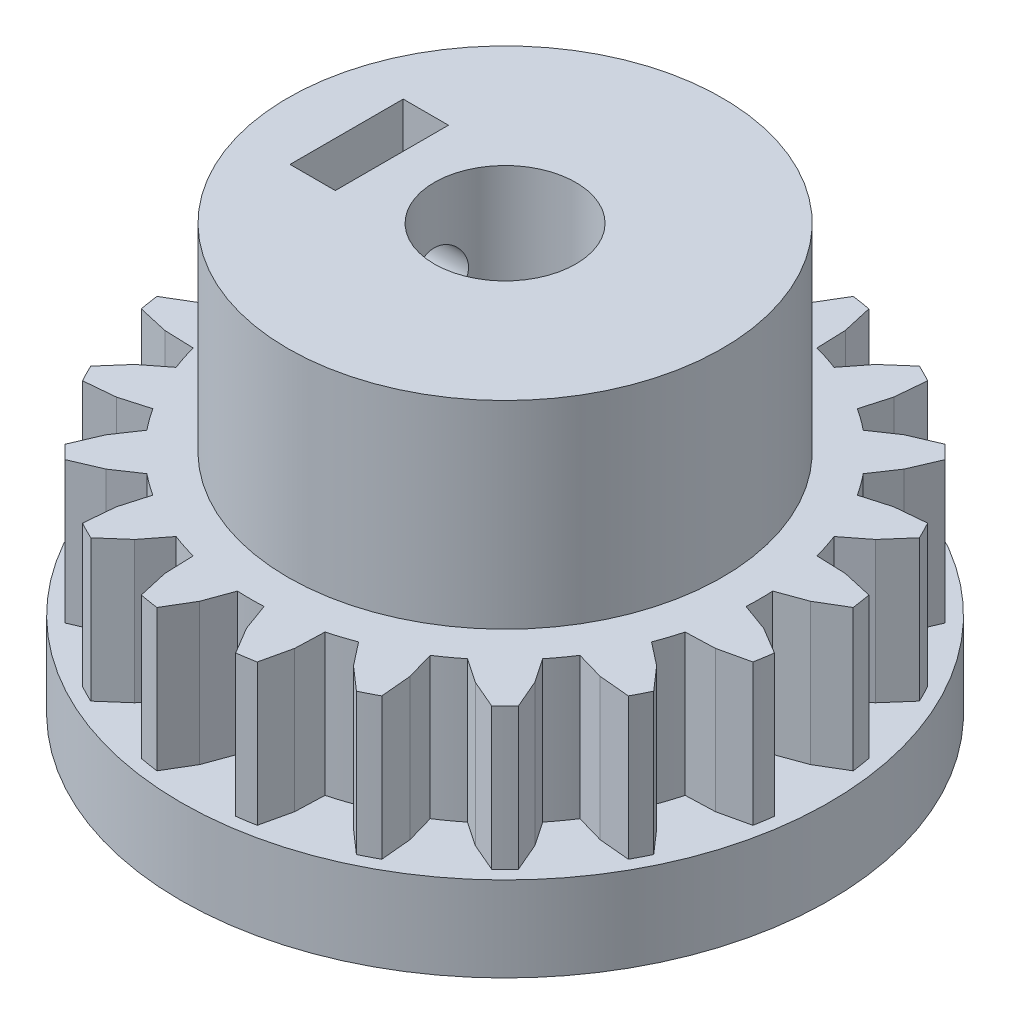
SolidWorks part; units mm, degrees
ref_plane "Ön Düzlem" through (0, 0, 0) normal (0, 0, 1) x (1, 0, 0)
ref_plane "Üst Düzlem" through (0, 0, 0) normal (0, 1, 0) x (1, 0, 0)
ref_plane "Sağ Düzlem" through (0, 0, 0) normal (1, 0, 0) x (0, 0, -1)
sketch "Çizim1" plane through (0, 0, 0) normal (0, 1, 0) x (1, 0, 0)
  line L0 (10.9117, -1.3908) -> (9.9657, -0.827)
  line L1 (9.9657, -0.827) -> (8.9877, -0.471)
  line L2 (8.9877, 0.471) -> (9.9657, 0.827)
  line L3 (9.9657, 0.827) -> (10.9117, 1.3908)
  line L4 (10.8074, 2.0492) -> (9.7335, 2.293)
  line L5 (9.7335, 2.293) -> (8.6933, 2.3294)
  line L6 (8.4022, 3.2253) -> (9.2224, 3.8661)
  line L7 (9.2224, 3.8661) -> (9.9479, 4.6946)
  line L8 (9.6452, 5.2886) -> (8.5486, 5.1886)
  line L9 (8.5486, 5.1886) -> (7.548, 4.9018)
  line L10 (6.9943, 5.6639) -> (7.5763, 6.5268)
  line L11 (7.5763, 6.5268) -> (8.0103, 7.5389)
  line L12 (7.5389, 8.0103) -> (6.5268, 7.5763)
  line L13 (6.5268, 7.5763) -> (5.6639, 6.9943)
  line L14 (4.9018, 7.548) -> (5.1886, 8.5486)
  line L15 (5.1886, 8.5486) -> (5.2886, 9.6452)
  line L16 (4.6946, 9.9479) -> (3.8661, 9.2224)
  line L17 (3.8661, 9.2224) -> (3.2253, 8.4022)
  line L18 (2.3294, 8.6933) -> (2.293, 9.7335)
  line L19 (2.293, 9.7335) -> (2.0492, 10.8074)
  line L20 (1.3908, 10.9117) -> (0.827, 9.9657)
  line L21 (0.827, 9.9657) -> (0.471, 8.9877)
  line L22 (-0.471, 8.9877) -> (-0.827, 9.9657)
  line L23 (-0.827, 9.9657) -> (-1.3908, 10.9117)
  line L24 (-2.0492, 10.8074) -> (-2.293, 9.7335)
  line L25 (-2.293, 9.7335) -> (-2.3294, 8.6933)
  line L26 (-3.2253, 8.4022) -> (-3.8661, 9.2224)
  line L27 (-3.8661, 9.2224) -> (-4.6946, 9.9479)
  line L28 (-5.2886, 9.6452) -> (-5.1886, 8.5486)
  line L29 (-5.1886, 8.5486) -> (-4.9018, 7.548)
  line L30 (-5.6639, 6.9943) -> (-6.5268, 7.5763)
  line L31 (-6.5268, 7.5763) -> (-7.5389, 8.0103)
  line L32 (-8.0103, 7.5389) -> (-7.5763, 6.5268)
  line L33 (-7.5763, 6.5268) -> (-6.9943, 5.6639)
  line L34 (-7.548, 4.9018) -> (-8.5486, 5.1886)
  line L35 (-8.5486, 5.1886) -> (-9.6452, 5.2886)
  line L36 (-9.9479, 4.6946) -> (-9.2224, 3.8661)
  line L37 (-9.2224, 3.8661) -> (-8.4022, 3.2253)
  line L38 (-8.6933, 2.3294) -> (-9.7335, 2.293)
  line L39 (-9.7335, 2.293) -> (-10.8074, 2.0492)
  line L40 (-10.9117, 1.3908) -> (-9.9657, 0.827)
  line L41 (-9.9657, 0.827) -> (-8.9877, 0.471)
  line L42 (-8.9877, -0.471) -> (-9.9657, -0.827)
  line L43 (-9.9657, -0.827) -> (-10.9117, -1.3908)
  line L44 (-10.8074, -2.0492) -> (-9.7335, -2.293)
  line L45 (-9.7335, -2.293) -> (-8.6933, -2.3294)
  line L46 (-8.4022, -3.2253) -> (-9.2224, -3.8661)
  line L47 (-9.2224, -3.8661) -> (-9.9479, -4.6946)
  line L48 (-9.6452, -5.2886) -> (-8.5486, -5.1886)
  line L49 (-8.5486, -5.1886) -> (-7.548, -4.9018)
  line L50 (-6.9943, -5.6639) -> (-7.5763, -6.5268)
  line L51 (-7.5763, -6.5268) -> (-8.0103, -7.5389)
  line L52 (-7.5389, -8.0103) -> (-6.5268, -7.5763)
  line L53 (-6.5268, -7.5763) -> (-5.6639, -6.9943)
  line L54 (-4.9018, -7.548) -> (-5.1886, -8.5486)
  line L55 (-5.1886, -8.5486) -> (-5.2886, -9.6452)
  line L56 (-4.6946, -9.9479) -> (-3.8661, -9.2224)
  line L57 (-3.8661, -9.2224) -> (-3.2253, -8.4022)
  line L58 (-2.3294, -8.6933) -> (-2.293, -9.7335)
  line L59 (-2.293, -9.7335) -> (-2.0492, -10.8074)
  line L60 (-1.3908, -10.9117) -> (-0.827, -9.9657)
  line L61 (-0.827, -9.9657) -> (-0.471, -8.9877)
  line L62 (0.471, -8.9877) -> (0.827, -9.9657)
  line L63 (0.827, -9.9657) -> (1.3908, -10.9117)
  line L64 (2.0492, -10.8074) -> (2.293, -9.7335)
  line L65 (2.293, -9.7335) -> (2.3294, -8.6933)
  line L66 (3.2253, -8.4022) -> (3.8661, -9.2224)
  line L67 (3.8661, -9.2224) -> (4.6946, -9.9479)
  line L68 (5.2886, -9.6452) -> (5.1886, -8.5486)
  line L69 (5.1886, -8.5486) -> (4.9018, -7.548)
  line L70 (5.6639, -6.9943) -> (6.5268, -7.5763)
  line L71 (6.5268, -7.5763) -> (7.5389, -8.0103)
  line L72 (8.0103, -7.5389) -> (7.5763, -6.5268)
  line L73 (7.5763, -6.5268) -> (6.9943, -5.6639)
  line L74 (7.548, -4.9018) -> (8.5486, -5.1886)
  line L75 (8.5486, -5.1886) -> (9.6452, -5.2886)
  line L76 (9.9479, -4.6946) -> (9.2224, -3.8661)
  line L77 (9.2224, -3.8661) -> (8.4022, -3.2253)
  line L78 (8.6933, -2.3294) -> (9.7335, -2.293)
  line L79 (9.7335, -2.293) -> (10.8074, -2.0492)
  arc A0 (8.9877, -0.471) -> (8.9877, 0.471) centre (0, 0) ccw
  arc A1 (10.9117, 1.3908) -> (10.8074, 2.0492) centre (0, 0) ccw
  arc A2 (8.6933, 2.3294) -> (8.4022, 3.2253) centre (0, 0) ccw
  arc A3 (9.9479, 4.6946) -> (9.6452, 5.2886) centre (0, 0) ccw
  arc A4 (7.548, 4.9018) -> (6.9943, 5.6639) centre (0, 0) ccw
  arc A5 (8.0103, 7.5389) -> (7.5389, 8.0103) centre (0, 0) ccw
  arc A6 (5.6639, 6.9943) -> (4.9018, 7.548) centre (0, 0) ccw
  arc A7 (5.2886, 9.6452) -> (4.6946, 9.9479) centre (0, 0) ccw
  arc A8 (3.2253, 8.4022) -> (2.3294, 8.6933) centre (0, 0) ccw
  arc A9 (2.0492, 10.8074) -> (1.3908, 10.9117) centre (0, 0) ccw
  arc A10 (0.471, 8.9877) -> (-0.471, 8.9877) centre (0, 0) ccw
  arc A11 (-1.3908, 10.9117) -> (-2.0492, 10.8074) centre (0, 0) ccw
  arc A12 (-2.3294, 8.6933) -> (-3.2253, 8.4022) centre (0, 0) ccw
  arc A13 (-4.6946, 9.9479) -> (-5.2886, 9.6452) centre (0, 0) ccw
  arc A14 (-4.9018, 7.548) -> (-5.6639, 6.9943) centre (0, 0) ccw
  arc A15 (-7.5389, 8.0103) -> (-8.0103, 7.5389) centre (0, 0) ccw
  arc A16 (-6.9943, 5.6639) -> (-7.548, 4.9018) centre (0, 0) ccw
  arc A17 (-9.6452, 5.2886) -> (-9.9479, 4.6946) centre (0, 0) ccw
  arc A18 (-8.4022, 3.2253) -> (-8.6933, 2.3294) centre (0, 0) ccw
  arc A19 (-10.8074, 2.0492) -> (-10.9117, 1.3908) centre (0, 0) ccw
  arc A20 (-8.9877, 0.471) -> (-8.9877, -0.471) centre (0, 0) ccw
  arc A21 (-10.9117, -1.3908) -> (-10.8074, -2.0492) centre (0, 0) ccw
  arc A22 (-8.6933, -2.3294) -> (-8.4022, -3.2253) centre (0, 0) ccw
  arc A23 (-9.9479, -4.6946) -> (-9.6452, -5.2886) centre (0, 0) ccw
  arc A24 (-7.548, -4.9018) -> (-6.9943, -5.6639) centre (0, 0) ccw
  arc A25 (-8.0103, -7.5389) -> (-7.5389, -8.0103) centre (0, 0) ccw
  arc A26 (-5.6639, -6.9943) -> (-4.9018, -7.548) centre (0, 0) ccw
  arc A27 (-5.2886, -9.6452) -> (-4.6946, -9.9479) centre (0, 0) ccw
  arc A28 (-3.2253, -8.4022) -> (-2.3294, -8.6933) centre (0, 0) ccw
  arc A29 (-2.0492, -10.8074) -> (-1.3908, -10.9117) centre (0, 0) ccw
  arc A30 (-0.471, -8.9877) -> (0.471, -8.9877) centre (0, 0) ccw
  arc A31 (1.3908, -10.9117) -> (2.0492, -10.8074) centre (0, 0) ccw
  arc A32 (2.3294, -8.6933) -> (3.2253, -8.4022) centre (0, 0) ccw
  arc A33 (4.6946, -9.9479) -> (5.2886, -9.6452) centre (0, 0) ccw
  arc A34 (4.9018, -7.548) -> (5.6639, -6.9943) centre (0, 0) ccw
  arc A35 (7.5389, -8.0103) -> (8.0103, -7.5389) centre (0, 0) ccw
  arc A36 (6.9943, -5.6639) -> (7.548, -4.9018) centre (0, 0) ccw
  arc A37 (9.6452, -5.2886) -> (9.9479, -4.6946) centre (0, 0) ccw
  arc A38 (8.4022, -3.2253) -> (8.6933, -2.3294) centre (0, 0) ccw
  arc A39 (10.8074, -2.0492) -> (10.9117, -1.3908) centre (0, 0) ccw
  circle A40 centre (0, 0) radius 11.4571
  circle A41 centre (0, 0) radius 2.5
  circle A42 centre (0, 0) radius 7.6751
  dimension "D1" = 5
extrude "Yükseklik-Ekstrüzyon1" add sketch "Çizim1" against normal blind 3 contours A40
extrude "Yükseklik-Ekstrüzyon2" add sketch "Çizim1<3>" along normal blind 5 contours L79 A39 L0 L1 A0 L2 L3 A1 L4 L5 A2 L6 L7 A3 L8 L9 A4 L10 L11 A5 L12 L13 A6 L14 L15 A7 L16 L17 A8 L18 L19 A9 L20 L21 A10 L22 L23 A11 L24 L25 A12 L26 L27 A13 L28 L29 A14 L30 L31 A15 L32 | A42 A41 | A41 region at (10.5597, 0, 1.6725) region at (0, 0, 0) region at (-7.458, 0, 0)
sketch "Çizim1<3>" plane through (0, 0, 0) normal (0, 1, 0) x (1, 0, 0) same geometry as "Çizim1"
extrude "Yükseklik-Ekstrüzyon3" add sketch "Çizim1<4>" along normal offset from surface (12 mm away) 7 contours A42 A41 region at (-7.458, 0, 0) up to face at (0, 5, 0) offset beyond the face yes
sketch "Çizim1<4>" plane through (0, 0, 0) normal (0, 1, 0) x (1, 0, 0) same geometry as "Çizim1"
sketch "Çizim3" plane through (0, -3, 0) normal (0, -1, 0) x (1, 0, 0)
  line L91 (0.3063, 1.4173) -> (0.1865, 1.327)
  line L92 (0.0962, 1.4468) -> (0.1865, 1.327)
  line L93 (0.5006, 1.3609) -> (0.3694, 1.2881)
  line L94 (0, 1.811) -> (0, -2.1215) construction
  line L95 (0.1061, 1.4461) -> (0, 1.34)
  line L96 (-0.1061, 1.4461) -> (0, 1.34)
  line L97 (0.2966, 1.4193) -> (0.3694, 1.2881)
  line L98 (0.6851, 1.278) -> (0.545, 1.2242)
  line L99 (0.4913, 1.3642) -> (0.545, 1.2242)
  line L100 (0.8563, 1.1702) -> (0.7101, 1.1364)
  line L101 (0.6764, 1.2826) -> (0.7101, 1.1364)
  line L102 (1.0108, 1.0396) -> (0.8614, 1.0265)
  line L103 (0.8483, 1.176) -> (0.8614, 1.0265)
  line L104 (1.1456, 0.8888) -> (0.9959, 0.8967)
  line L105 (1.0037, 1.0465) -> (0.9959, 0.8967)
  line L106 (1.2582, 0.7207) -> (1.111, 0.7493)
  line L107 (1.1396, 0.8966) -> (1.111, 0.7493)
  line L108 (1.3463, 0.5386) -> (1.2044, 0.5874)
  line L109 (1.2533, 0.7293) -> (1.2044, 0.5874)
  line L110 (1.4081, 0.346) -> (1.2745, 0.4141)
  line L111 (1.3426, 0.5477) -> (1.2745, 0.4141)
  line L112 (1.4426, 0.1467) -> (1.3197, 0.2327)
  line L113 (1.4057, 0.3556) -> (1.3197, 0.2327)
  line L114 (1.4489, -0.0555) -> (1.3392, 0.0468)
  line L115 (1.4415, 0.1565) -> (1.3392, 0.0468)
  line L116 (1.4271, -0.2566) -> (1.3327, -0.1401)
  line L117 (1.4493, -0.0457) -> (1.3327, -0.1401)
  line L118 (1.3775, -0.4528) -> (1.3002, -0.3242)
  line L119 (1.4288, -0.2469) -> (1.3002, -0.3242)
  line L120 (1.3011, -0.6401) -> (1.2425, -0.502)
  line L121 (1.3805, -0.4434) -> (1.2425, -0.502)
  line L122 (1.1993, -0.8149) -> (1.1605, -0.67)
  line L123 (1.3054, -0.6312) -> (1.1605, -0.67)
  line L124 (1.0743, -0.9739) -> (1.056, -0.825)
  line L125 (1.2049, -0.8067) -> (1.056, -0.825)
  line L126 (0.9283, -1.1139) -> (0.9309, -0.964)
  line L127 (1.0809, -0.9666) -> (0.9309, -0.964)
  line L128 (0.7642, -1.2323) -> (0.7877, -1.0841)
  line L129 (0.9358, -1.1076) -> (0.7877, -1.0841)
  line L130 (0.5853, -1.3266) -> (0.6291, -1.1832)
  line L131 (0.7726, -1.227) -> (0.6291, -1.1832)
  line L132 (0.3949, -1.3952) -> (0.4583, -1.2592)
  line L133 (0.5943, -1.3226) -> (0.4583, -1.2592)
  line L134 (0.1969, -1.4366) -> (0.2786, -1.3108)
  line L135 (0.4044, -1.3925) -> (0.2786, -1.3108)
  line L136 (-0.0049, -1.45) -> (0.0935, -1.3368)
  line L137 (0.2067, -1.4352) -> (0.0935, -1.3368)
  line L138 (-0.2067, -1.4352) -> (-0.0935, -1.3368)
  line L139 (0.0049, -1.45) -> (-0.0935, -1.3368)
  line L140 (-0.4044, -1.3925) -> (-0.2786, -1.3108)
  line L141 (-0.1969, -1.4366) -> (-0.2786, -1.3108)
  line L142 (-0.5943, -1.3226) -> (-0.4583, -1.2592)
  line L143 (-0.3949, -1.3952) -> (-0.4583, -1.2592)
  line L144 (-0.7726, -1.227) -> (-0.6291, -1.1832)
  line L145 (-0.5853, -1.3266) -> (-0.6291, -1.1832)
  line L146 (-0.9358, -1.1076) -> (-0.7877, -1.0841)
  line L147 (-0.7642, -1.2323) -> (-0.7877, -1.0841)
  line L148 (-1.0809, -0.9666) -> (-0.9309, -0.964)
  line L149 (-0.9283, -1.1139) -> (-0.9309, -0.964)
  line L150 (-1.2049, -0.8067) -> (-1.056, -0.825)
  line L151 (-1.0743, -0.9739) -> (-1.056, -0.825)
  line L152 (-1.3054, -0.6312) -> (-1.1605, -0.67)
  line L153 (-1.1993, -0.8149) -> (-1.1605, -0.67)
  line L154 (-1.3805, -0.4434) -> (-1.2425, -0.502)
  line L155 (-1.3011, -0.6401) -> (-1.2425, -0.502)
  line L156 (-1.4288, -0.2469) -> (-1.3002, -0.3242)
  line L157 (-1.3775, -0.4528) -> (-1.3002, -0.3242)
  line L158 (-1.4493, -0.0457) -> (-1.3327, -0.1401)
  line L159 (-1.4271, -0.2566) -> (-1.3327, -0.1401)
  line L160 (-1.4415, 0.1565) -> (-1.3392, 0.0468)
  line L161 (-1.4489, -0.0555) -> (-1.3392, 0.0468)
  line L162 (-1.4057, 0.3556) -> (-1.3197, 0.2327)
  line L163 (-1.4426, 0.1467) -> (-1.3197, 0.2327)
  line L164 (-1.3426, 0.5477) -> (-1.2745, 0.4141)
  line L165 (-1.4081, 0.346) -> (-1.2745, 0.4141)
  line L166 (-1.2533, 0.7293) -> (-1.2044, 0.5874)
  line L167 (-1.3463, 0.5386) -> (-1.2044, 0.5874)
  line L168 (-1.1396, 0.8966) -> (-1.111, 0.7493)
  line L169 (-1.2582, 0.7207) -> (-1.111, 0.7493)
  line L170 (-1.0037, 1.0465) -> (-0.9959, 0.8967)
  line L171 (-1.1456, 0.8888) -> (-0.9959, 0.8967)
  line L172 (-0.8483, 1.176) -> (-0.8614, 1.0265)
  line L173 (-1.0108, 1.0396) -> (-0.8614, 1.0265)
  line L174 (-0.6764, 1.2826) -> (-0.7101, 1.1364)
  line L175 (-0.8563, 1.1702) -> (-0.7101, 1.1364)
  line L176 (-0.4913, 1.3642) -> (-0.545, 1.2242)
  line L177 (-0.6851, 1.278) -> (-0.545, 1.2242)
  line L178 (-0.2966, 1.4193) -> (-0.3694, 1.2881)
  line L179 (-0.5006, 1.3609) -> (-0.3694, 1.2881)
  line L180 (-0.0962, 1.4468) -> (-0.1865, 1.327)
  line L181 (-0.3063, 1.4173) -> (-0.1865, 1.327)
  circle A6 centre (0, 0) radius 1.45
  point P285 (0, 0)
  dimension "D4" = 45
  dimension "D5" = 2.9
  dimension "D3" = 0.15
  dimension "D6" = 45
extrude "Kes-Ekstrüzyon3" cut sketch "Çizim3" against normal blind 3.1 contours L94 L96 L180 L181 L178 L179 L176 L177 L174 L175 L172 L173 L170 L171 L168 L169 L166 L167 L164 L165 L162 L163 L160 L161 L158 L159 L156 L157 L154 L155 L152 L153 L150 L151 L148 L149 L146 L147 L144 L145 L142 L143 L140 L141 L138 L139 | L95 L94 L136 L137 L134 L135 L132 L133 L130 L131 L128 L129 L126 L127 L124 L125 L122 L123 L120 L121 L118 L119 L116 L117 L114 L115 L112 L113 L110 L111 L108 L109 L106 L107 L104 L105 L102 L103 L100 L101 L98 L99 L93 L97 L91 L92 region at (0.5906, -3, 0) region at (-0.5906, -3, 0)
sketch "Çizim4" plane through (0, 0, 0) normal (1, 0, 0) x (0, 0, -1)
  line L0 (7.6751, 12) -> (-7.6751, 12) construction
  circle A0 centre (0, 9) radius 1
  dimension "D1" = 2
  dimension "D2" = 3
extrude "Kes-Ekstrüzyon4" cut sketch "Çizim4" against normal through all
sketch "Çizim6" plane through (0, 12, 0) normal (0, 1, 0) x (1, 0, 0)
  line L1 (-5.6, 2) -> (-4, 2)
  line L2 (-5.6, 2) -> (-5.6, -2)
  line L3 (-5.6, -2) -> (-4, -2)
  line L4 (-4, 2) -> (-4, -2)
  point P4 (-4, 0)
  dimension "D1" = 4
  dimension "D2" = 1.6
  dimension "D3" = 4
extrude "Kes-Ekstrüzyon5" cut sketch "Çizim6" against normal blind 5
